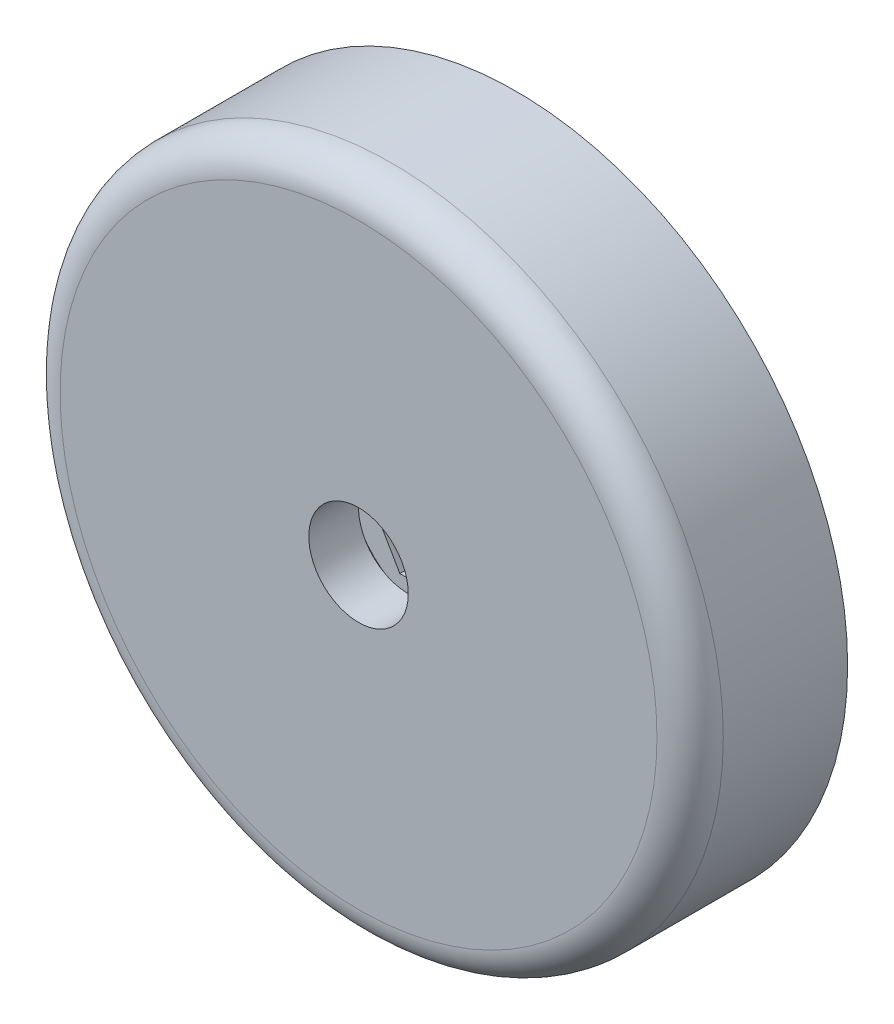
SolidWorks part; units mm, degrees
ref_plane "Front Plane" through (0, 0, 0) normal (0, 0, 1) x (1, 0, 0)
ref_plane "Top Plane" through (0, 0, 0) normal (0, 1, 0) x (1, 0, 0)
ref_plane "Right Plane" through (0, 0, 0) normal (1, 0, 0) x (0, 0, -1)
sketch "Sketch1" plane through (0, 0, 0) normal (0, 0, 1) x (1, 0, 0)
  circle A0 centre (-11.8226, 14.5298) radius 20
  circle A1 centre (-11.8226, 14.5298) radius 1
  dimension "D1" = 40
  dimension "D2" = 2
extrude "Boss-Extrude1" add sketch "Sketch1" along normal blind 22.5
hole_wizard "Tap Drill for M5x0.8 Tap1" positions "Sketch2" profile "Sketch3" hole size "M5x0.8" standard "ANSI Metric"
sketch "Sketch2" plane through (0, 0, 22.5) normal (0, 0, 1) x (1, 0, 0)
  point P0 (-11.8226, 14.5298)
sketch "Sketch3" plane through (-11.8226, 14.5298, 22.5) normal (1, 0, 0) x (0, -1, 0)
  line L0 (0, 0) -> (0, 6.2618)
  line L1 (0, 6.2618) -> (2.1, 5)
  line L2 (2.1, 5) -> (2.1, 0)
  line L5 (2.1, 0) -> (0, 0)
  line L10 (0, 6.2618) -> (-2.1, 5) construction
  line L11 (0, -6.35) -> (0, 107.95) construction
  dimension "Hole Dia." = 4.2
  dimension "Hole Depth" = 5
  dimension "Drill Angle" = 118
sketch "Sketch4" plane through (0, 0, 22.5) normal (0, 0, 1) x (1, 0, 0)
  line L1 (6.1774, 17.8338) -> (3.3834, 17.8338)
  line L2 (6.1774, 17.8338) -> (6.1774, 11.2298)
  line L3 (6.1774, 11.2298) -> (3.3834, 11.2298)
  line L4 (3.3834, 17.8338) -> (3.3834, 11.2298)
  circle A0 centre (-11.8226, 14.5298) radius 1 construction
  circle A1 centre (-11.8226, 14.5298) radius 20 construction
  dimension "D1" = 6.604
  dimension "D2" = 2.794
  dimension "D3" = 3.3
  dimension "D4" = 18
extrude "Cut-Extrude1" cut sketch "Sketch4" against normal blind 20.5
ref_axis "Axis1" through (-11.8226, 14.5298, 22.5) along (0, 0, -1)
pattern_circular "CirPattern1" count 5 over 360 about axis through (-11.8226, 14.5298, 22.5) along (0, 0, -1) of "Cut-Extrude1"
sketch "Sketch6" plane through (0, 0, 22.5) normal (0, 0, 1) x (1, 0, 0)
  line L0 (-9.5126, 18.5298) -> (-7.2008, 14.5298)
  line L1 (-14.1326, 18.5298) -> (-9.5126, 18.5298)
  line L2 (-14.1326, 18.5298) -> (-14.1326, 10.5298)
  line L3 (-14.1326, 10.5298) -> (-9.5126, 10.5298)
  line L4 (-9.5126, 18.5298) -> (-9.5126, 10.5298)
  line L5 (-7.2008, 14.5298) -> (-9.5126, 10.5298)
  line L6 (-14.1326, 10.5298) -> (-16.4444, 14.5298)
  line L7 (-16.4444, 14.5298) -> (-14.1326, 18.5298)
  point P4 (-11.8226, 10.5298)
  circle M30 centre (-11.8226, 14.5298) radius 2.1
  dimension "D1" = 8
  dimension "D2" = 4
  dimension "D3" = 4.62
  dimension "D4" = 2.31
  dimension "D5" = 4.62
  dimension "D6" = 4.62
  dimension "D7" = 4.62
  dimension "D8" = 4.62
extrude "Cut-Extrude3" cut sketch "Sketch6" against normal blind 6 contours L7 L6 L2 | L5 L0 L4 | L4 L1 L2 L3 M30 | M30 region at (-9.6049, 14.5298, 22.5) region at (-8.742, 14.5298, 22.5) region at (-14.9032, 14.5298, 22.5) region at (-11.8226, 14.5298, 22.5)
sketch "Sketch7" plane through (0, 0, 22.5) normal (0, 0, 1) x (1, 0, 0)
  circle A0 centre (-11.8226, 14.5298) radius 5.5
  dimension "D1" = 11
extrude "Cut-Extrude4" cut sketch "Sketch7" against normal blind 1.8
sketch "Sketch9" plane through (0, 0, 16.5) normal (0, 0, 1) x (1, 0, 0)
  circle A0 centre (-11.8226, 14.5298) radius 3.014
  dimension "D1" = 6.028
extrude "Cut-Extrude5" cut sketch "Sketch9" against normal blind 2
chamfer "Chamfer1" distance 2 angle 45 1 edges at (-8.8085, 14.5298, 14.5)
sketch "Sketch8" plane through (0, 0, 22.5) normal (0, 0, 1) x (1, 0, 0)
  circle A0 centre (-11.8226, 14.5298) radius 3
  circle A1 centre (-11.8226, 14.5298) radius 20
  dimension "D1" = 6
extrude "Boss-Extrude2" add sketch "Sketch8" along normal blind 3
sketch "Sketch5" plane through (0, 0, 0) normal (0, 0, -1) x (-1, 0, 0)
  circle A0 centre (11.8226, 14.5298) radius 5
  circle A1 centre (11.8226, 14.5298) radius 6
  dimension "D1" = 10
  dimension "D2" = 12
extrude "Cut-Extrude2" cut sketch "Sketch5" against normal blind 1
fillet "Fillet3" radius 0.5 2 edges at (-16.8226, 14.5298, 1) (-17.8226, 14.5298, 1)
fillet "Fillet4" radius 2 1 edges at (8.1774, 14.5298, 25.5)
sketch "Sketch10" plane through (0, 0, 0) normal (0, 0, -1) x (-1, 0, 0)
  line L1 (-9.8157, -9.8898) -> (34.0222, -9.8898)
  line L2 (-9.8157, -9.8898) -> (-9.8157, 38.0052)
  line L3 (-9.8157, 38.0052) -> (34.0222, 38.0052)
  line L4 (34.0222, -9.8898) -> (34.0222, 38.0052)
extrude "Cut-Extrude6" cut sketch "Sketch10" against normal blind 16
equation "\"D2@Sketch4\"=25.4*.11"
equation "\"D3@Sketch4\"=6.6/2"
equation "\"oringdiameter\"= 11"
equation "\"oringthickness\"= 2"
equation "\"D2@Sketch5\"=\"oringdiameter\" + \"oringthickness\"/2"
equation "\"D1@Sketch5\"=\"oringdiameter\" - \"oringthickness\"/2"
equation "\"D1@Cut-Extrude2\"= \"oringthickness\"/2"
equation "\"D1@Sketch4\"=25.4*.26"
equation "\"D3@Sketch6\"=4.62"
